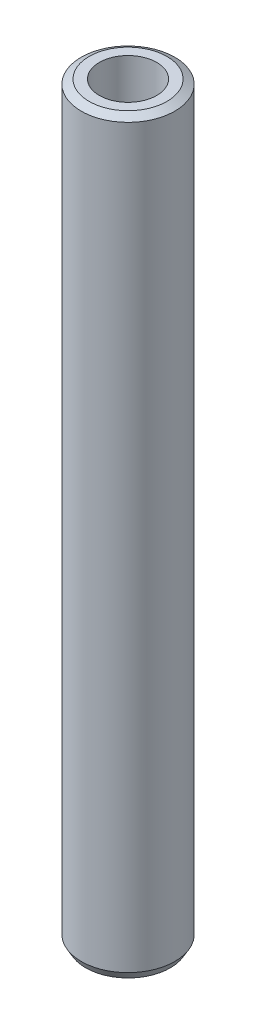
SolidWorks part; units mm, degrees
ref_plane "Front Plane" through (0, 0, 0) normal (0, 0, 1) x (1, 0, 0)
ref_plane "Top Plane" through (0, 0, 0) normal (0, 1, 0) x (1, 0, 0)
ref_plane "Right Plane" through (0, 0, 0) normal (1, 0, 0) x (0, 0, -1)
sketch "Sketch1" plane through (0, 0, 0) normal (0, 1, 0) x (1, 0, 0)
  circle A0 centre (0, 0) radius 37.5
  dimension "SHAFT_OD" = 75
extrude "Boss-Extrude1" add sketch "Sketch1" along normal blind 600
sketch "Sketch2" plane through (0, 0, 0) normal (0, 1, 0) x (1, 0, 0)
  circle A0 centre (0, 0) radius 22.9926
  dimension "BORE_D" = 45.9853
extrude "Cut-Extrude1" cut sketch "Sketch2" along normal through all
chamfer "Chamfer1" distance 3.6323 angle 60 2 edges at (0, 600, 37.5) (0, 0, 37.5) first distance on face at (0, 600, 37.5) first distance on face at (0, 0, 22.9926)
